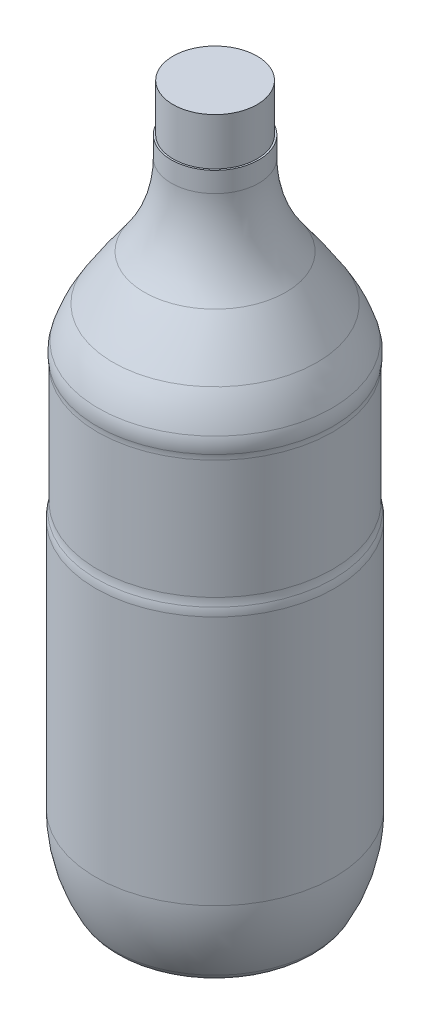
SolidWorks part; units mm, degrees
ref_plane "Front Plane" through (0, 0, 0) normal (0, 0, 1) x (1, 0, 0)
ref_plane "Top Plane" through (0, 0, 0) normal (0, 1, 0) x (1, 0, 0)
ref_plane "Right Plane" through (0, 0, 0) normal (1, 0, 0) x (0, 0, -1)
sketch "Sketch11" plane through (0, 0, 0) normal (0, 0, 1) x (1, 0, 0)
  line L0 (-52.7054, 81.4345) -> (-52.7054, 67.4345)
  line L1 (-75.7054, 81.4345) -> (-40.2054, 81.4345) construction
  line L2 (-75.7054, 81.4345) -> (-75.7054, -131.0655) construction
  line L3 (-75.7054, -131.0655) -> (-40.2054, -131.0655) construction
  line L4 (-40.2054, 81.4345) -> (-40.2054, -131.0655) construction
  line L5 (-52.7054, 67.4345) -> (-53.2054, 67.4345)
  line L6 (-53.2054, 67.4345) -> (-53.2054, 61.4345)
  line L7 (-52.7054, 81.4345) -> (-40.2054, 81.4345)
  line L8 (-75.7054, 11.561) -> (-75.1554, 11.561)
  line L9 (-75.1554, 11.561) -> (-75.1554, -28.439)
  line L10 (-75.1554, -28.439) -> (-75.7054, -28.439)
  line L11 (-75.7054, -106.0655) -> (-75.7054, -28.439)
  line L12 (-40.2054, -122.8957) -> (-40.2054, 81.4345)
  line L13 (-40.2054, 81.4345) -> (-40.2054, -123.5655)
  arc A0 (-53.2054, 61.4345) -> (-61.2552, 37.3682) centre (-93.2054, 61.4345) cw
  arc A1 (-61.2552, 37.3682) -> (-70.5394, 23.9345) centre (98.4957, -82.9632) ccw
  arc A2 (-70.5394, 23.9345) -> (-75.7054, 11.561) centre (-36.7324, 2.555) ccw
  arc A3 (-75.7054, -106.0655) -> (-70.0039, -127.9886) centre (-30.7054, -106.0655) ccw
  arc A4 (-70.0039, -127.9886) -> (-60.7805, -129.5523) centre (-64.7641, -125.0655) ccw
  arc A5 (-60.7805, -129.5523) -> (-40.2054, -123.5655) centre (-44.1823, -148.2471) cw
  dimension "D7" = 40
  dimension "D8" = 200
  dimension "D13" = 25
  dimension "D14" = 45
  dimension "D15" = 6
  dimension "D16" = 25
  dimension "D17" = 7.5
  dimension "D1" = 212.5
  dimension "D2" = 35.5
  dimension "D3" = 0.5
  dimension "D4" = 14
  dimension "D5" = 6
  dimension "D6" = 12.5
  dimension "D10" = 57.5
  dimension "D11" = 40
  dimension "D12" = 1.1
revolve "Revolve3" add sketch "Sketch11" angle 360 about L12 region at (-56.5406, -35.9277, 0)
fillet "Fillet1" radius 10 1 edges at (-4.7054, -28.439, 0)
fillet "Fillet2" radius 10 1 edges at (-5.2554, -28.439, 0)
fillet "Fillet3" radius 10 1 edges at (-5.2554, 11.561, 0)
fillet "Fillet4" radius 10 1 edges at (-4.7054, 11.561, 0)
